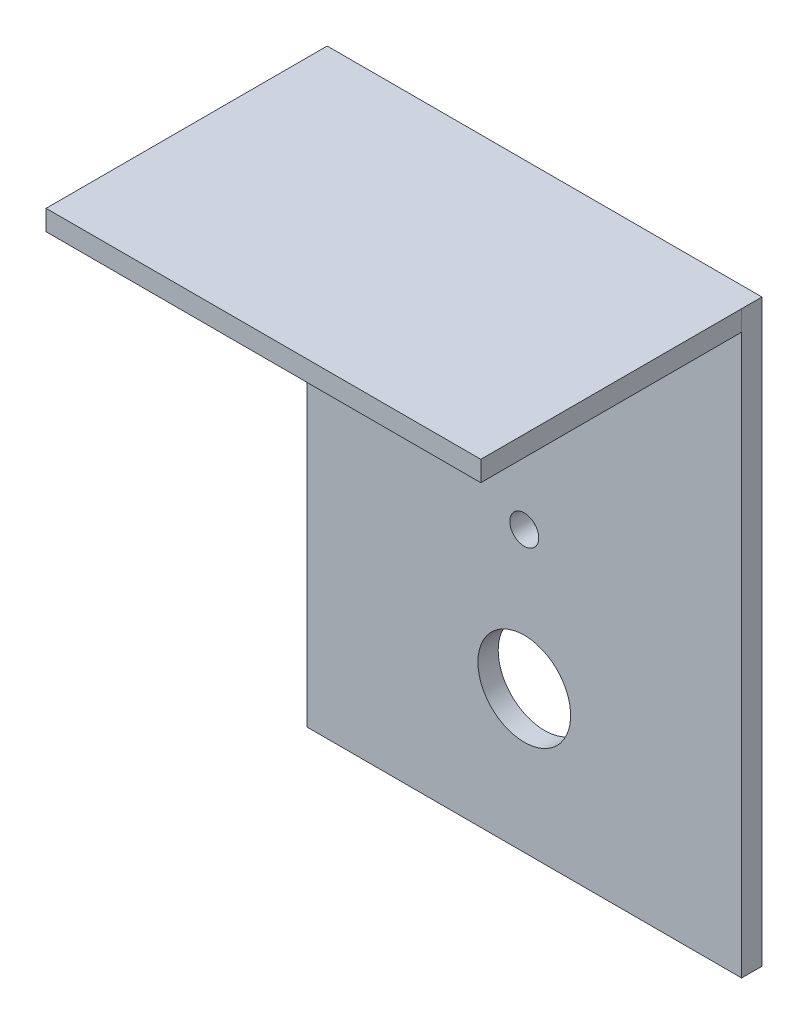
SolidWorks part; units mm, degrees
ref_plane "Front Plane" through (0, 0, 0) normal (0, 0, 1) x (1, 0, 0)
ref_plane "Top Plane" through (0, 0, 0) normal (0, 1, 0) x (1, 0, 0)
ref_plane "Right Plane" through (0, 0, 0) normal (1, 0, 0) x (0, 0, -1)
sketch "Sketch1" plane through (0, 0, 0) normal (0, 1, 0) x (1, 0, 0)
  line L1 (0, 0) -> (75, 0)
  line L2 (0, 0) -> (0, 45)
  line L3 (0, 45) -> (75, 45)
  line L4 (75, 0) -> (75, 45)
  dimension "D1" = 45
  dimension "D2" = 75
extrude "Boss-Extrude1" add sketch "Sketch1" along normal blind 3.5 contours L3 L4 L1 L2
sketch "Sketch2" plane through (0, 0, -45) normal (0, 0, -1) x (-1, 0, 0)
  line L1 (0, 3.5) -> (-74.9993, 3.5)
  line L2 (0, 3.5) -> (0, -96.5)
  line L3 (0, -96.5) -> (-74.9993, -96.5)
  line L4 (-74.9993, 3.5) -> (-74.9993, -96.5)
  dimension "D1" = 100
  dimension "D2" = 74.9993
extrude "Boss-Extrude2" add sketch "Sketch2" along normal blind 3.5
sketch "Sketch3" plane through (0, 0, -48.5) normal (0, 0, -1) x (-1, 0, 0)
  line L0 (-37.5, 3.5) -> (-37.4997, -96.5) construction
  line L1 (0, 3.5) -> (-75, 3.5) construction
  line L2 (-74.9993, -96.5) -> (0, -96.5) construction
  line L3 (0, -48.25) -> (-74.9993, -48.25) construction
  line L4 (0, -96.5) -> (0, 0) construction
  line L5 (-74.9993, 0) -> (-74.9993, -96.5) construction
  circle A0 centre (-37.4999, -24.4706) radius 8
  circle A1 centre (-37.4999, -72.0294) radius 8
  circle A2 centre (-37.4997, -48.25) radius 2.5
  dimension "D1" = 16
  dimension "D2" = 5
extrude "Cut-Extrude2" cut sketch "Sketch3" against normal through all
